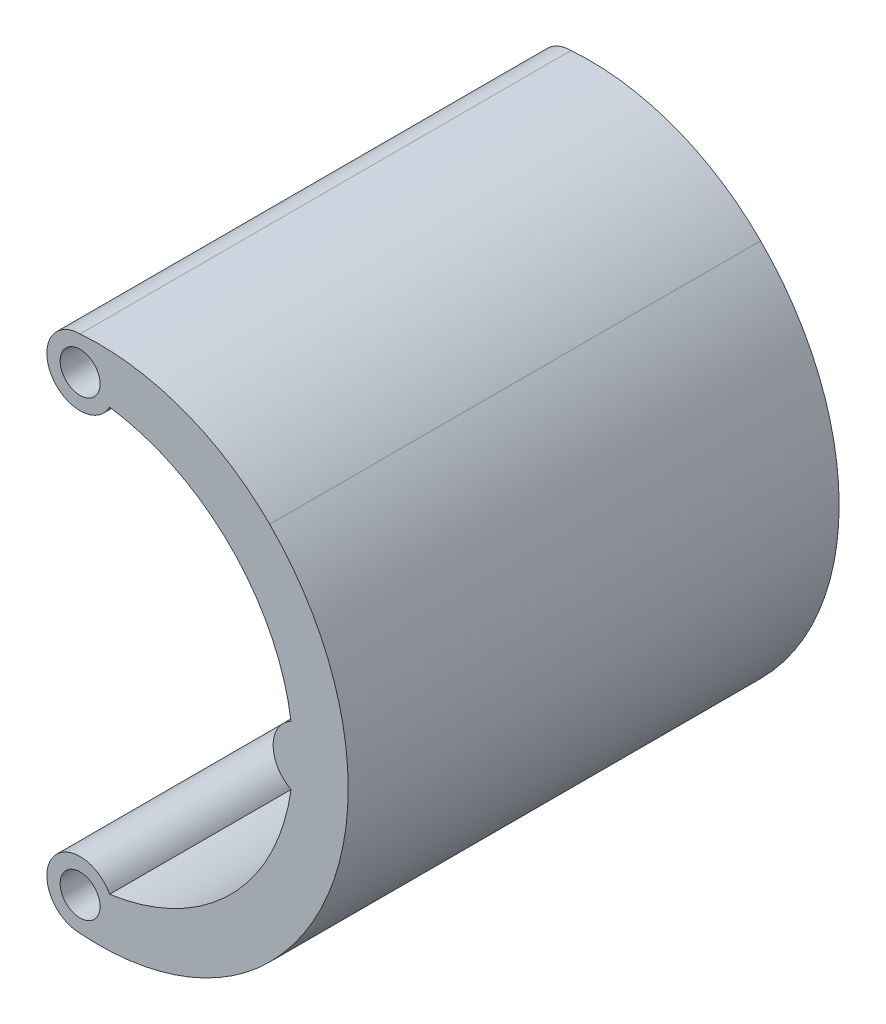
SolidWorks part; units mm, degrees
ref_plane "Front Plane" through (0, 0, 0) normal (1, 0, 0) x (0, 1, 0)
ref_plane "Top Plane" through (0, 0, 0) normal (0, 0, 1) x (0, 1, 0)
ref_plane "Right Plane" through (0, 0, 0) normal (0, 1, 0) x (-1, 0, 0)
sketch "Sketch1" plane through (0, 0, 0) normal (0, 0, 1) x (0, 1, 0)
  line L0 (0, -17) -> (0, 17) construction
  line L1 (-17, 0) -> (17, 0) construction
  line L2 (0, 0) -> (1.4142, 1.4142) construction
  line L3 (0, 0) -> (-1.4142, -1.4142) construction
  line L4 (0, 0) -> (-1.4142, -1.4142) construction
  line L5 (0, 0) -> (1.4142, -1.4142) construction
  circle A0 centre (0, 17) radius 2.5
  circle A1 centre (0, -17) radius 2.5
  circle A2 centre (-17, 0) radius 2.5
  circle A3 centre (17, 0) radius 2.5
  arc A4 (15.8456, -2.2175) -> (2.2175, -15.8456) centre (0, 0) cw
  arc A5 (0, -19.5) -> (19.5, 0) centre (1.4142, -1.4142) ccw
  arc A6 (-19.5, 0) -> (0, -19.5) centre (-1.4142, -1.4142) ccw
  arc A7 (-2.2175, -15.8456) -> (-15.8456, -2.2175) centre (0, 0) cw
  circle A8 centre (0, 0) radius 13.75 construction
  arc A9 (-14.2418, -14.2418) -> (14.2418, -14.2418) centre (0, 0) ccw
  point P4 (0, 0)
  point P8 (0, 0)
  point P12 (0, 0)
  point P15 (5.9498, -18.9791)
  point P22 (0, 0)
  dimension "D3" = 5
  dimension "D4" = 5
  dimension "D5" = 2
  dimension "D6" = 45
  dimension "D7" = 16
  dimension "D8" = 2
  dimension "D9" = 27.5
  dimension "D11" = 90
  dimension "D1" = 34
  dimension "D2" = 34
  dimension "D10" = 2
extrude "Boss-Extrude1" add sketch "Sketch1" along normal blind 36.881 contours A0 A3 | A3 | A2 | A1 | A1 A7 A2 | A6 A9 A5 region at (17, 0, 0) region at (11.8979, 11.8979, 0) region at (11.8979, -11.8979, 0) region at (18.4596, 7.7075, 0) region at (0, 17, 0) region at (0, -17, 0)
hole_wizard "Ø3.0mm Dowel Hole1" positions "Sketch3" profile "Sketch5" hole size "Ø3.0" standard "ANSI Metric" end condition through all
sketch "Sketch3" plane through (0, 0, 0) normal (0, 0, 1) x (1, 0, 0)
  point P0 (0, 17)
  point P3 (0, -17)
sketch "Sketch5" plane through (0, 17, 0) normal (1, 0, 0) x (0, 1, 0)
  line L0 (0, 0) -> (0, 36.881)
  line L1 (0, 36.881) -> (1.5, 36.881)
  line L2 (1.5, 36.881) -> (1.5, 0.021)
  line L3 (1.5, 0.021) -> (1.525, 0)
  line L5 (1.525, 0) -> (0, 0)
  line L6 (-1.5, 0.021) -> (-1.525, 0) construction
  line L11 (0, -6.35) -> (0, 107.95) construction
  dimension "Thru Hole Dia." = 3
  dimension "Thru Hole Depth" = 36.881
  dimension "Near C'Sink Dia." = 3.05
  dimension "Near C'Sink Angle" = 100
sketch "Sketch7" plane through (0, 0, 0) normal (0, 0, -1) x (1, 0, 0)
  circle A0 centre (-17, 0) radius 1.715
  circle A1 centre (17, 0) radius 1.715
  dimension "D1" = 3.43
extrude "Cut-Extrude2" cut sketch "Sketch7" against normal blind 5
equation "\"Alum Bracket Thickness\"= 0.35in"
equation "\"D1@Boss-Extrude1\"=35"
equation "\"spur gear gap\"= 0.094in"
